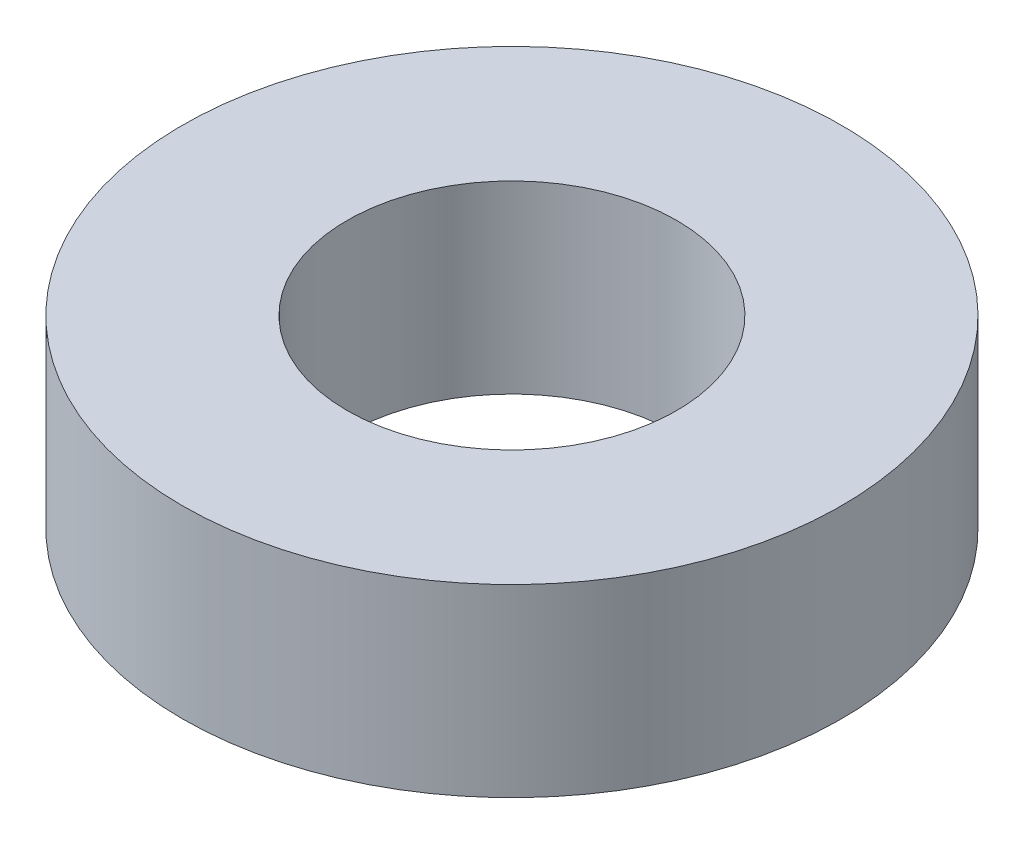
SolidWorks part; units mm, degrees
ref_plane "Front Plane" through (0, 0, 0) normal (0, 0, 1) x (1, 0, 0)
ref_plane "Top Plane" through (0, 0, 0) normal (0, 1, 0) x (1, 0, 0)
ref_plane "Right Plane" through (0, 0, 0) normal (1, 0, 0) x (0, 0, -1)
sketch "Sketch1" plane through (0, 0, 0) normal (0, 1, 0) x (1, 0, 0)
  circle A0 centre (0, 0) radius 50
  dimension "FLANGE_OD" = 100
extrude "Boss-Extrude1" add sketch "Sketch1" along normal blind 28
sketch "Sketch2" plane through (0, 0, 0) normal (0, 1, 0) x (1, 0, 0)
  circle A0 centre (0, 0) radius 25
  dimension "BORE_D" = 50
extrude "Cut-Extrude1" cut sketch "Sketch2" along normal through all
sketch "Sketch3" plane through (0, 28, 0) normal (0, 1, 0) x (1, 0, 0)
  circle A0 centre (0, 0) radius 16.8465 construction
  circle A1 centre (-16.8465, 0) radius 3.4296
  dimension "BOLT_D" = 6.8593
  dimension "BOLT_PCD" = 33.6931
extrude "Cut-Extrude2" cut sketch "Sketch3" against normal blind 25.7809 rebuild error yes
pattern_circular "CirPattern1" count 8 over 360 rebuild error yes
